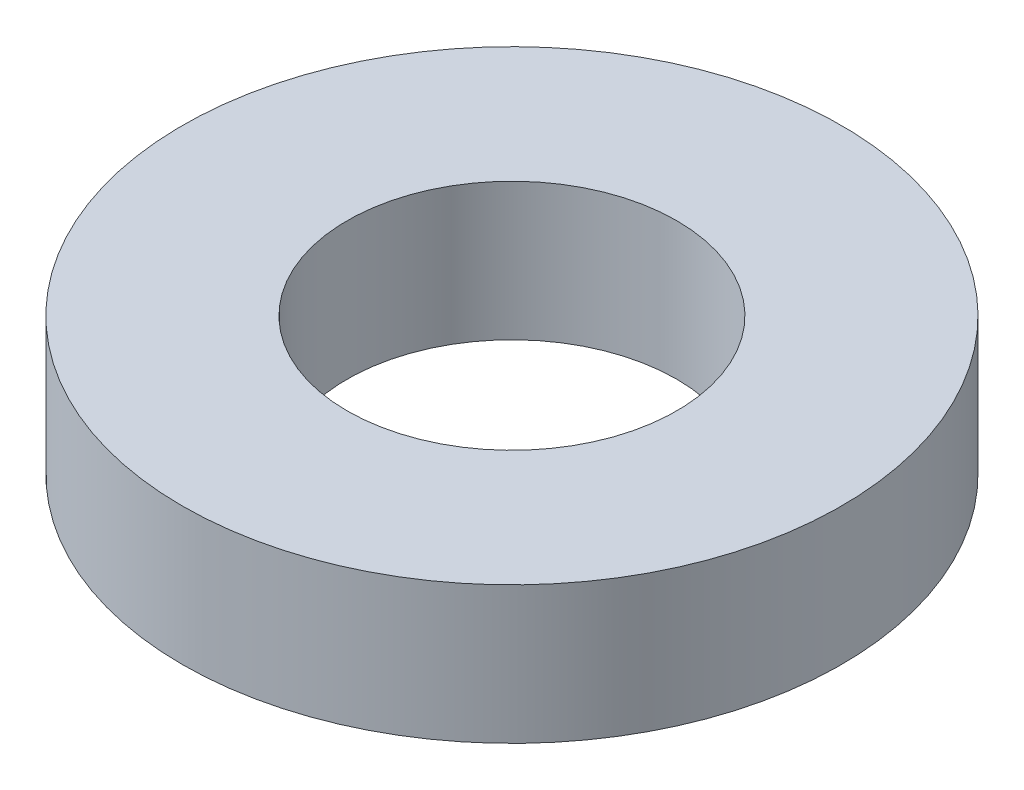
SolidWorks part; units mm, degrees
ref_plane "Front Plane" through (0, 0, 0) normal (0, 0, 1) x (1, 0, 0)
ref_plane "Top Plane" through (0, 0, 0) normal (0, 1, 0) x (1, 0, 0)
ref_plane "Right Plane" through (0, 0, 0) normal (1, 0, 0) x (0, 0, -1)
ref_axis "X-Axis" through (88.99, 0, 0) along (-1, 0, 0)
ref_axis "Y-Axis" through (0, 0, -88.99) along (0, 0, 1)
ref_axis "Z-Axis" through (0, -55, 0) along (0, 1, 0)
sketch "Sketch1" plane through (0, 0, 0) normal (0, 1, 0) x (1, 0, 0)
  circle A0 centre (0, 0) radius 6
  circle A1 centre (0, 0) radius 12
  dimension "D1" = 24
  dimension "D2" = 12
extrude "Boss-Extrude1" add sketch "Sketch1" along normal blind 5
